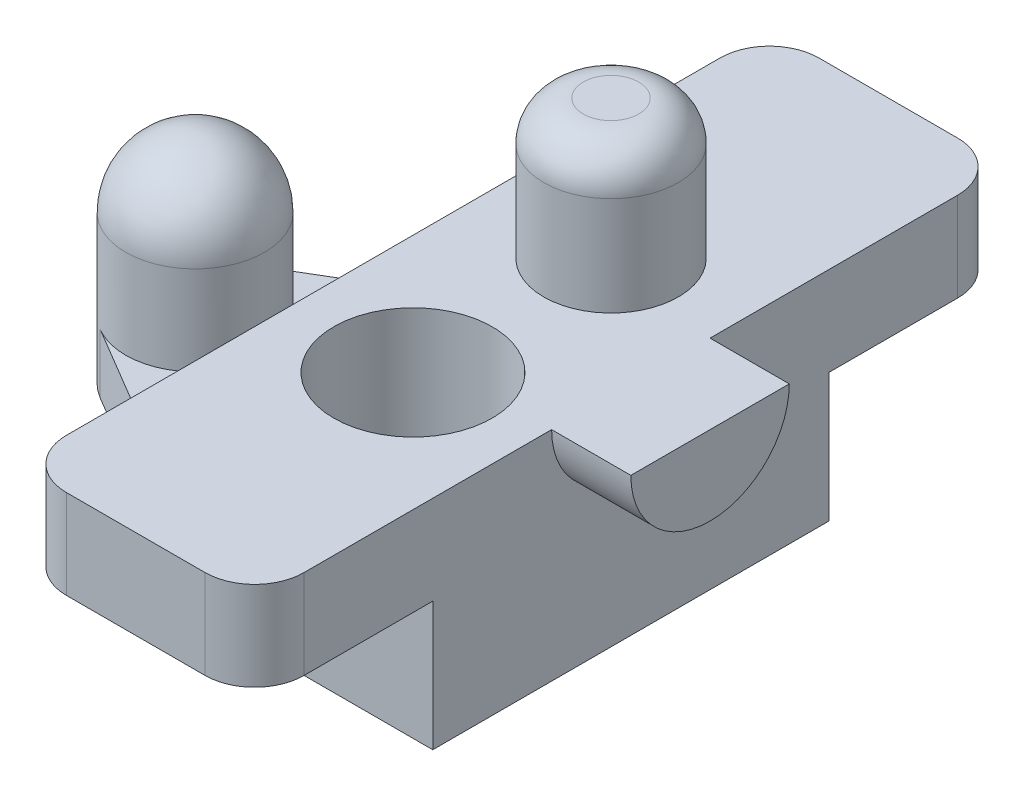
SolidWorks part; units mm, degrees
other "Markup1"
sketch "Sketch7" plane through (12, 7.5, 6.5) normal (0.0383, 0.9456, 0.3232) x (0.9932, -0.0006, -0.1161)
ref_plane "Front Plane" through (0, 0, 0) normal (0, 0, 1) x (1, 0, 0)
ref_plane "Top Plane" through (0, 0, 0) normal (0, 1, 0) x (1, 0, 0)
ref_plane "Right Plane" through (0, 0, 0) normal (1, 0, 0) x (0, 0, -1)
sketch "Sketch1" plane through (0, 0, 0) normal (0, 1, 0) x (1, 0, 0)
  line L0 (5, 5) -> (11, 5)
  line L1 (11, 5) -> (11, -5)
  line L2 (11, -5) -> (5, -5)
  line L3 (5, -5) -> (-0.8927, -1.5052)
  line L4 (5, 5) -> (-0.8927, 1.5052)
  arc A0 (-0.8927, 1.5052) -> (-0.8927, -1.5052) centre (0, 0) ccw
  point P11 (11, 0)
  dimension "D1" = 10
  dimension "D4" = 5
  dimension "D5" = 1.75
  dimension "D2" = 6
  dimension "D3" = 6
extrude "Boss-Extrude1" add sketch "Sketch1" against normal blind 1.5 contours L1 L2 L3 A0 L4 L0
sketch "Sketch2" plane through (0, 0, 0) normal (0, 1, 0) x (1, 0, 0)
  line L1 (5, 5) -> (11, 5)
  line L2 (5, 5) -> (5, -5)
  line L3 (5, -5) -> (11, -5)
  line L4 (11, 5) -> (11, -5)
  circle A0 centre (0, 0) radius 1.75
  dimension "D1" = 3.5
extrude "Boss-Extrude2" add sketch "Sketch2" along normal blind 4
sketch "Sketch3" plane through (0, 4, 0) normal (0, 1, 0) x (1, 0, 0)
  line L0 (5, 5) -> (11, 5)
  line L4 (-55, 0) -> (55, 0) construction
  line L6 (5, -5) -> (11, -5)
  line L7 (5, 5) -> (5, 8.25)
  line L8 (6.25, 9.5) -> (9.75, 9.5)
  line L9 (11, 8.25) -> (11, 5)
  line L10 (11, -8.25) -> (11, -5)
  line L11 (6.25, -9.5) -> (9.75, -9.5)
  line L12 (5, -5) -> (5, -8.25)
  arc A4 (5, 8.25) -> (6.25, 9.5) centre (6.25, 8.25) cw
  arc A5 (11, 8.25) -> (9.75, 9.5) centre (9.75, 8.25) ccw
  arc A6 (11, -8.25) -> (9.75, -9.5) centre (9.75, -8.25) cw
  arc A7 (5, -8.25) -> (6.25, -9.5) centre (6.25, -8.25) ccw
  dimension "D2" = 1.25
  dimension "D1" = 4.5
extrude "Boss-Extrude3" add sketch "Sketch3" against normal blind 2.25
fillet "Fillet1" radius 1.75 1 edges at (0, 4, 1.75)
sketch "Sketch4" plane through (0, 4, 0) normal (0, 1, 0) x (1, 0, 0)
  line L0 (5, 8.25) -> (5, -8.25) construction
  circle A0 centre (8, 2.5) radius 1.7
  dimension "D1" = 3.4
  dimension "D2" = 3
  dimension "D3" = 2.5
extrude "Boss-Extrude4" add sketch "Sketch4" along normal blind 3.5
fillet "Fillet2" radius 1 1 edges at (8, 7.5, -0.8)
sketch "Sketch5" plane through (0, 4, 0) normal (0, 1, 0) x (1, 0, 0)
  line L0 (5, 8.25) -> (5, -8.25) construction
  circle A0 centre (8, -2.5) radius 2
  dimension "D1" = 4
  dimension "D2" = 2.5
  dimension "D3" = 3
extrude "Cut-Extrude1" cut sketch "Sketch5" against normal blind 3.75
sketch "Sketch6" plane through (11, 0, 0) normal (1, 0, 0) x (0, 0, -1)
  line L0 (-8.25, 4) -> (8.25, 4) construction
  line L1 (-2, 4) -> (2, 4)
  arc A0 (-2, 4) -> (2, 4) centre (0, 4) ccw
  dimension "D1" = 4
extrude "Boss-Extrude5" add sketch "Sketch6" along normal blind 2
